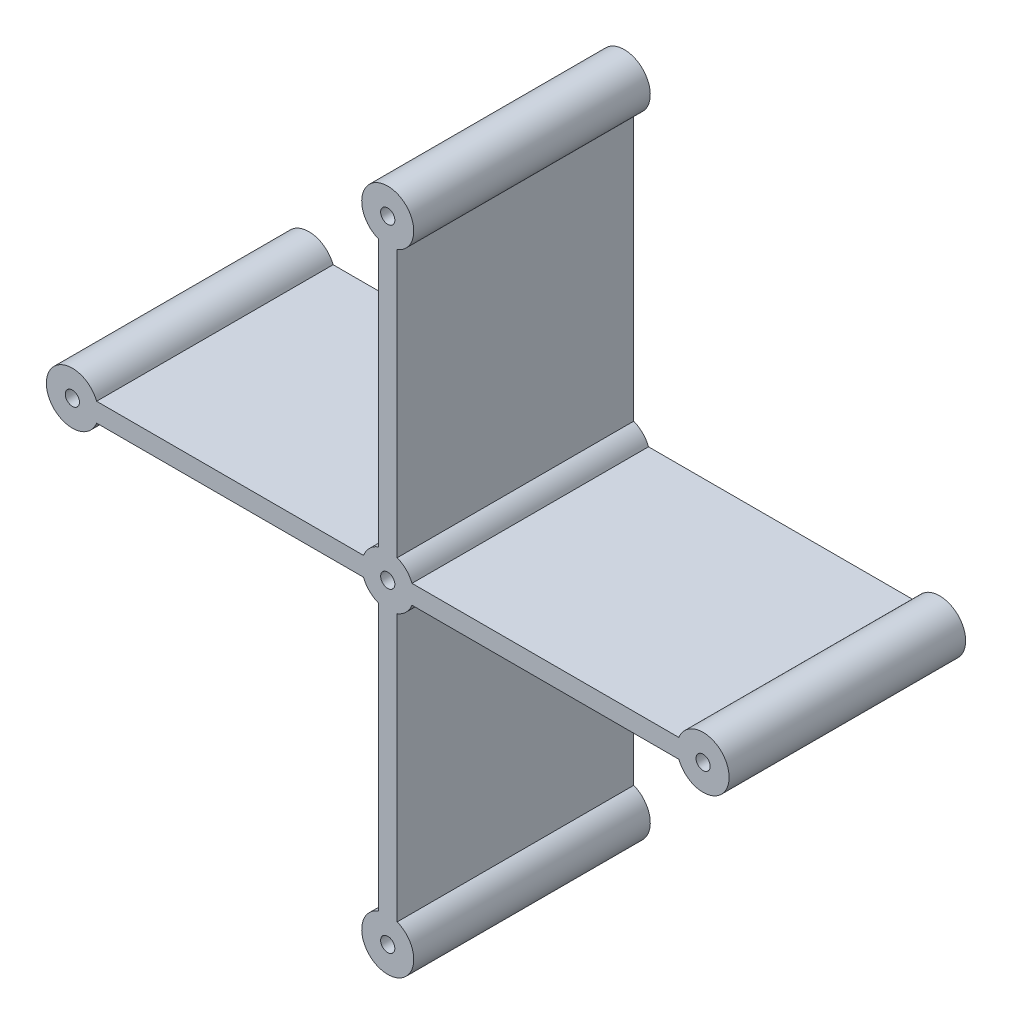
SolidWorks part; units mm, degrees
ref_plane "Front Plane" through (0, 0, 0) normal (0, 0, 1) x (1, 0, 0)
ref_plane "Top Plane" through (0, 0, 0) normal (0, 1, 0) x (1, 0, 0)
ref_plane "Right Plane" through (0, 0, 0) normal (1, 0, 0) x (0, 0, -1)
sketch "Sketch1" plane through (0, 0, 0) normal (0, 0, 1) x (1, 0, 0)
  line L0 (0, 0) -> (0, 40) construction
  line L1 (-1.2, 0) -> (-1.2, 40)
  line L2 (1.2, 0) -> (1.2, 40)
  line L3 (0, 0) -> (40, 0) construction
  line L4 (0, 1.2) -> (40, 1.2)
  line L5 (0, -1.2) -> (40, -1.2)
  line L6 (0, 0) -> (0, -40) construction
  line L7 (1.2, 0) -> (1.2, -40)
  line L8 (-1.2, 0) -> (-1.2, -40)
  line L9 (0, 0) -> (-40, 0) construction
  line L10 (0, -1.2) -> (-40, -1.2)
  line L11 (0, 1.2) -> (-40, 1.2)
  circle A0 centre (0, 0) radius 3.3
  circle A1 centre (0, 0) radius 0.9
  arc A2 (-1.2, 0) -> (1.2, 0) centre (0, 0) ccw
  arc A3 (1.2, 40) -> (-1.2, 40) centre (0, 40) ccw
  circle A4 centre (0, 40) radius 0.9
  circle A5 centre (0, 40) radius 3.3
  circle A6 centre (40, 0) radius 0.9
  circle A7 centre (40, 0) radius 3.3
  arc A8 (0, 1.2) -> (0, -1.2) centre (0, 0) ccw
  arc A9 (40, -1.2) -> (40, 1.2) centre (40, 0) ccw
  circle A10 centre (0, -40) radius 0.9
  circle A11 centre (0, -40) radius 3.3
  arc A12 (1.2, 0) -> (-1.2, 0) centre (0, 0) ccw
  arc A13 (-1.2, -40) -> (1.2, -40) centre (0, -40) ccw
  circle A14 centre (-40, 0) radius 0.9
  circle A15 centre (-40, 0) radius 3.3
  arc A16 (0, -1.2) -> (0, 1.2) centre (0, 0) ccw
  arc A17 (-40, 1.2) -> (-40, -1.2) centre (-40, 0) ccw
  circle A18 centre (0, 0) radius 27.4
  circle A19 centre (0, 0) radius 25
  point P4 (0, 20)
  point P16 (20, 0)
  point P25 (0, -20)
  point P34 (-20, 0)
  point P43 (0, 0)
  dimension "D2" = 1.8
  dimension "D1" = 6.6
  dimension "D7" = 50
  dimension "D3" = 2.4
  dimension "D4" = 40
  dimension "D6" = 2.4
  dimension "D5" = 4
extrude "Boss-Extrude1" add sketch "Sketch1" along normal blind 30 contours L2 A3 L1 A2 | L4 A9 L5 A8 | L7 A13 L8 A12 | L10 A17 L11 A16 | A0 | A5 | A7 | A11 | A15
extrude "Cut-Extrude1" cut sketch "Sketch1<3>" along normal blind 30 contours A10 | A6 | A1 | A14 | A4
sketch "Sketch1<3>" plane through (0, 0, 0) normal (0, 0, 1) x (1, 0, 0) same geometry as "Sketch1"
equation "\"D6@Sketch1\"=\"D3@Sketch1\""
